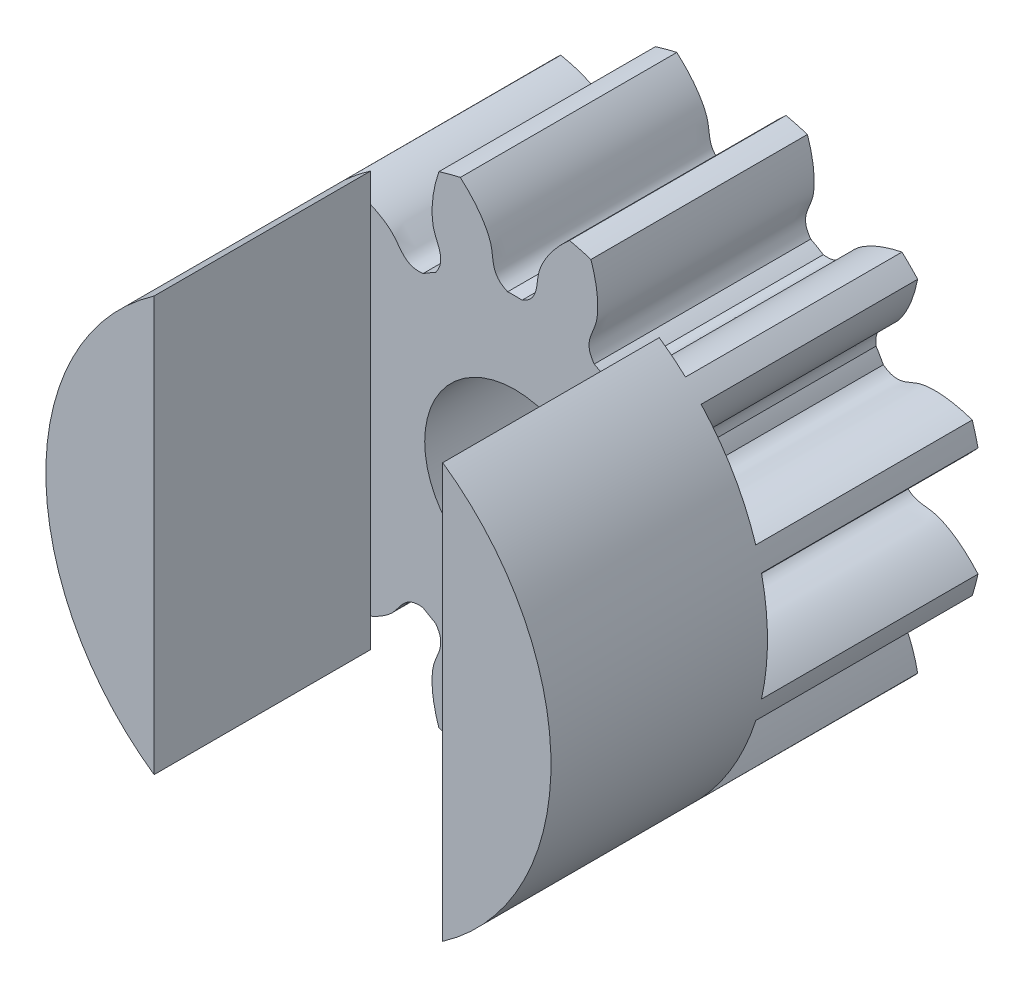
SolidWorks part; units mm, degrees
note: '?' marks a value the reader was unsure of.
ref_plane "前视基准面" through (0, 0, 0) normal (0, 0, 1) x (1, 0, 0)
ref_plane "上视基准面" through (0, 0, 0) normal (0, 1, 0) x (1, 0, 0)
ref_plane "右视基准面" through (0, 0, 0) normal (1, 0, 0) x (0, 0, -1)
sketch "草图1" plane through (0, 0, 0) normal (0, 0, 1) x (1, 0, 0)
  circle A0 centre (0, 0) radius 35
extrude "凸台-拉伸1" add sketch "草图1" along normal blind 30
ref_axis "基准轴1" through (0, 0, -1.5) along (0, 0, 1)?
sketch "草图2" plane through (0, 0, 0) normal (0, 0, 1) x (1, 0, 0)
  line L0 (0, 0) -> (0, 35) construction
  circle A0 centre (0, 0) radius 35 construction
  arc A1 (1.0042, 23.7288) -> (-1.0042, 23.7288) centre (0, 0) ccw
  arc A2 (17.488, 39.4749) -> (-17.488, 39.4749) centre (0, 0) ccw
  spline S0 degree 3 poles (1.0042, 23.7288) (3.4039, 24.7465) (2.8719, 26.7241) (3.3808, 28.4474) (3.4131, 28.5495) (3.4511, 28.6617) (3.4952, 28.7836) (3.5458, 28.9152) (3.6032, 29.0562) (3.6679, 29.2064) (3.7402, 29.3655) (3.8206, 29.5333) (3.9094, 29.7096) (4.0069, 29.894) (4.1136, 30.0862) (4.2298, 30.2861) (4.3558, 30.4932) (4.492, 30.7073) (4.6387, 30.928) (4.7962, 31.155) (4.9648, 31.3879) (5.1449, 31.6265) (5.3366, 31.8702) (5.5403, 32.1188) (5.7563, 32.3718) (5.9848, 32.6289) (6.226, 32.8897) (6.4802, 33.1537) (6.7476, 33.4205) (7.0285, 33.6897) (7.323, 33.9609) (7.6312, 34.2336) (7.9535, 34.5075) (8.2899, 34.7819) (8.6406, 35.0565) (9.0058, 35.3308) (9.3855, 35.6044) (9.7799, 35.8767) (10.189, 36.1473) (10.6131, 36.4157) (11.052, 36.6814) (11.5059, 36.9439) (11.9749, 37.2028) (12.4589, 37.4574) (12.958, 37.7074) (13.4722, 37.9522) (14.0015, 38.1913) (14.5458, 38.4242) (15.1051, 38.6504) (15.6793, 38.8694) (16.4719, 39.1536) (17.078, 39.3505) (17.488, 39.4749) knots 0 0 0 0 0.218015 0.222044 0.226546 0.231522 0.236972 0.242897 0.249295 0.256167 0.263513 0.271332 0.279626 0.288394 0.297636 0.307351 0.317541 0.328204 0.339341 0.350953 0.363038 0.375597 0.38863 0.402137 0.416118 0.430573 0.445502 0.460904 0.476781 0.493132 0.509956 0.527255 0.545027 0.563273 0.581994 0.601188 0.620856 0.640998 0.661614 0.682704 0.704268 0.726305 0.748817 0.771803 0.795262 0.819196 0.843603 0.868484 0.89384 0.919669 0.945972 1 1 1 1
  spline S1 degree 3 poles (-1.0042, 23.7288) (-3.4039, 24.7465) (-2.8719, 26.7241) (-3.3808, 28.4474) (-3.4131, 28.5495) (-3.4511, 28.6617) (-3.4952, 28.7836) (-3.5458, 28.9152) (-3.6032, 29.0562) (-3.6679, 29.2064) (-3.7402, 29.3655) (-3.8206, 29.5333) (-3.9094, 29.7096) (-4.0069, 29.894) (-4.1136, 30.0862) (-4.2298, 30.2861) (-4.3558, 30.4932) (-4.492, 30.7073) (-4.6387, 30.928) (-4.7962, 31.155) (-4.9648, 31.3879) (-5.1449, 31.6265) (-5.3366, 31.8702) (-5.5403, 32.1188) (-5.7563, 32.3718) (-5.9848, 32.6289) (-6.226, 32.8897) (-6.4802, 33.1537) (-6.7476, 33.4205) (-7.0285, 33.6897) (-7.323, 33.9609) (-7.6312, 34.2336) (-7.9535, 34.5075) (-8.2899, 34.7819) (-8.6406, 35.0565) (-9.0058, 35.3308) (-9.3855, 35.6044) (-9.7799, 35.8767) (-10.189, 36.1473) (-10.6131, 36.4157) (-11.052, 36.6814) (-11.5059, 36.9439) (-11.9749, 37.2028) (-12.4589, 37.4574) (-12.958, 37.7074) (-13.4722, 37.9522) (-14.0015, 38.1913) (-14.5458, 38.4242) (-15.1051, 38.6504) (-15.6793, 38.8694) (-16.4719, 39.1536) (-17.078, 39.3505) (-17.488, 39.4749) knots 0 0 0 0 0.218015 0.222044 0.226546 0.231522 0.236972 0.242897 0.249295 0.256167 0.263513 0.271332 0.279626 0.288394 0.297636 0.307351 0.317541 0.328204 0.339341 0.350953 0.363038 0.375597 0.38863 0.402137 0.416118 0.430573 0.445502 0.460904 0.476781 0.493132 0.509956 0.527255 0.545027 0.563273 0.581994 0.601188 0.620856 0.640998 0.661614 0.682704 0.704268 0.726305 0.748817 0.771803 0.795262 0.819196 0.843603 0.868484 0.89384 0.919669 0.945972 1 1 1 1
extrude "切除-拉伸1" cut sketch "草图2" along normal through all
pattern_circular "阵列(圆周)1" count 12 every 30 about axis through (0, 0, -1.5) along (0, 0, 1) of "切除-拉伸1"
sketch "草图3" plane through (0, 0, 0) normal (0, 0, 1) x (1, 0, 0)
  circle A0 centre (0, 0) radius 30 construction
  dimension "Dn" = 60
sketch "草图4" plane through (0, 0, 30) normal (0, 0, 1) x (1, 0, 0)
  circle A0 centre (0, 0) radius 1.3486
  arc M1 (-10.9947, 21.0518) -> (-12.734, 20.0476) centre (0, 0) ccw
  spline M2 degree 3 poles (-12.734, 20.0476) (-15.3212, 19.7292) (-15.8492, 21.7078) (-17.1515, 22.9458) (-17.2306, 23.0181) (-17.3196, 23.0962) (-17.4188, 23.1797) (-17.5283, 23.2684) (-17.6486, 23.3618) (-17.7797, 23.4595) (-17.9219, 23.5612) (-18.0754, 23.6663) (-18.2404, 23.7746) (-18.4171, 23.8855) (-18.6056, 23.9986) (-18.8062, 24.1136) (-19.0189, 24.23) (-19.2439, 24.3473) (-19.4813, 24.4651) (-19.7312, 24.5829) (-19.9936, 24.7003) (-20.2688, 24.8169) (-20.5567, 24.9321) (-20.8575, 25.0455) (-21.171, 25.1567) (-21.4974, 25.2651) (-21.8367, 25.3703) (-22.1889, 25.4718) (-22.5539, 25.5692) (-22.9317, 25.6619) (-23.3223, 25.7495) (-23.7257, 25.8316) (-24.1417, 25.9076) (-24.5702, 25.9771) (-25.0113, 26.0395) (-25.4647, 26.0945) (-25.9303, 26.1416) (-26.408, 26.1802) (-26.8976, 26.21) (-27.399, 26.2304) (-27.912, 26.241) (-28.4364, 26.2414) (-28.9719, 26.2311) (-29.5185, 26.2096) (-30.0757, 26.1765) (-30.6434, 26.1314) (-31.2213, 26.0739) (-31.8091, 26.0034) (-32.4066, 25.9197) (-33.0134, 25.8222) (-33.8419, 25.6721) (-34.4652, 25.5396) (-34.8825, 25.4422) knots 0 0 0 0 0.218015 0.222044 0.226546 0.231522 0.236972 0.242897 0.249295 0.256167 0.263513 0.271332 0.279626 0.288394 0.297636 0.307351 0.317541 0.328204 0.339341 0.350953 0.363038 0.375597 0.38863 0.402137 0.416118 0.430573 0.445502 0.460904 0.476781 0.493132 0.509956 0.527255 0.545027 0.563273 0.581994 0.601188 0.620856 0.640998 0.661614 0.682704 0.704268 0.726305 0.748817 0.771803 0.795262 0.819196 0.843603 0.868484 0.89384 0.919669 0.945972 1 1 1 1 only from (-12.734, 20.0476) to (-23.6368, 25.8128)
  arc M3 (-23.6368, 25.8128) -> (-25.8128, 23.6368) centre (0, 0) ccw
  spline M4 degree 3 poles (-25.4422, 34.8825) (-25.5396, 34.4652) (-25.6721, 33.8419) (-25.8222, 33.0134) (-25.9197, 32.4066) (-26.0034, 31.8091) (-26.0739, 31.2213) (-26.1314, 30.6434) (-26.1765, 30.0757) (-26.2096, 29.5185) (-26.2311, 28.9719) (-26.2414, 28.4364) (-26.241, 27.912) (-26.2304, 27.399) (-26.21, 26.8976) (-26.1802, 26.408) (-26.1416, 25.9303) (-26.0945, 25.4647) (-26.0395, 25.0113) (-25.9771, 24.5702) (-25.9076, 24.1417) (-25.8316, 23.7257) (-25.7495, 23.3223) (-25.6619, 22.9317) (-25.5692, 22.5539) (-25.4718, 22.1889) (-25.3703, 21.8367) (-25.2651, 21.4974) (-25.1567, 21.171) (-25.0455, 20.8575) (-24.9321, 20.5567) (-24.8169, 20.2688) (-24.7003, 19.9936) (-24.5829, 19.7312) (-24.4651, 19.4813) (-24.3473, 19.2439) (-24.23, 19.0189) (-24.1136, 18.8062) (-23.9986, 18.6056) (-23.8855, 18.4171) (-23.7746, 18.2404) (-23.6663, 18.0754) (-23.5612, 17.9219) (-23.4595, 17.7797) (-23.3618, 17.6486) (-23.2684, 17.5283) (-23.1797, 17.4188) (-23.0962, 17.3196) (-23.0181, 17.2306) (-22.9458, 17.1515) (-21.7078, 15.8492) (-19.7292, 15.3212) (-20.0476, 12.734) knots 0 0 0 0 0.054028 0.080331 0.10616 0.131516 0.156397 0.180804 0.204738 0.228197 0.251183 0.273695 0.295732 0.317296 0.338386 0.359002 0.379144 0.398812 0.418006 0.436727 0.454973 0.472745 0.490044 0.506868 0.523219 0.539096 0.554498 0.569427 0.583882 0.597863 0.61137 0.624403 0.636962 0.649047 0.660659 0.671796 0.682459 0.692649 0.702364 0.711606 0.720374 0.728668 0.736487 0.743833 0.750705 0.757103 0.763028 0.768478 0.773454 0.777956 0.781985 1 1 1 1 only from (-25.8128, 23.6368) to (-20.0476, 12.734)
  arc M5 (-20.0476, 12.734) -> (-21.0518, 10.9947) centre (0, 0) ccw
  spline M6 degree 3 poles (-21.0518, 10.9947) (-23.1331, 9.4254) (-24.5797, 10.8749) (-26.3266, 11.2959) (-26.4312, 11.3189) (-26.5473, 11.3421) (-26.675, 11.3649) (-26.8142, 11.3869) (-26.965, 11.4077) (-27.1274, 11.4267) (-27.3014, 11.4436) (-27.4869, 11.4579) (-27.6839, 11.4692) (-27.8924, 11.4769) (-28.1123, 11.4806) (-28.3434, 11.4799) (-28.5858, 11.4743) (-28.8393, 11.4634) (-29.1038, 11.4468) (-29.3791, 11.4239) (-29.6652, 11.3943) (-29.9618, 11.3576) (-30.2687, 11.3135) (-30.5858, 11.2613) (-30.913, 11.2008) (-31.2498, 11.1315) (-31.5963, 11.053) (-31.952, 10.9648) (-32.3168, 10.8666) (-32.6904, 10.758) (-33.0725, 10.6386) (-33.4628, 10.508) (-33.8611, 10.3658) (-34.267, 10.2117) (-34.6802, 10.0453) (-35.1003, 9.8662) (-35.5271, 9.6741) (-35.9601, 9.4687) (-36.399, 9.2497) (-36.8435, 9.0167) (-37.293, 8.7694) (-37.7473, 8.5075) (-38.206, 8.2308) (-38.6685, 7.939) (-39.1346, 7.6317) (-39.6037, 7.3088) (-40.0754, 6.97) (-40.5492, 6.6151) (-41.0248, 6.2438) (-41.5015, 5.856) (-42.144, 5.3117) (-42.6175, 4.8853) (-42.9302, 4.5924) knots 0 0 0 0 0.218015 0.222044 0.226546 0.231522 0.236972 0.242897 0.249295 0.256167 0.263513 0.271332 0.279626 0.288394 0.297636 0.307351 0.317541 0.328204 0.339341 0.350953 0.363038 0.375597 0.38863 0.402137 0.416118 0.430573 0.445502 0.460904 0.476781 0.493132 0.509956 0.527255 0.545027 0.563273 0.581994 0.601188 0.620856 0.640998 0.661614 0.682704 0.704268 0.726305 0.748817 0.771803 0.795262 0.819196 0.843603 0.868484 0.89384 0.919669 0.945972 1 1 1 1 only from (-21.0518, 10.9947) to (-33.3765, 10.5362)
  arc M7 (-33.3765, 10.5362) -> (-34.173, 7.5637) centre (0, 0) ccw
  spline M8 degree 3 poles (-39.4749, 17.488) (-39.3505, 17.078) (-39.1536, 16.4719) (-38.8694, 15.6793) (-38.6504, 15.1051) (-38.4242, 14.5458) (-38.1913, 14.0015) (-37.9522, 13.4722) (-37.7074, 12.958) (-37.4574, 12.4589) (-37.2028, 11.9749) (-36.9439, 11.5059) (-36.6814, 11.052) (-36.4157, 10.6131) (-36.1473, 10.189) (-35.8767, 9.7799) (-35.6044, 9.3855) (-35.3308, 9.0058) (-35.0565, 8.6406) (-34.7819, 8.2899) (-34.5075, 7.9535) (-34.2336, 7.6312) (-33.9609, 7.323) (-33.6897, 7.0285) (-33.4205, 6.7476) (-33.1537, 6.4802) (-32.8897, 6.226) (-32.6289, 5.9848) (-32.3718, 5.7563) (-32.1188, 5.5403) (-31.8702, 5.3366) (-31.6265, 5.1449) (-31.3879, 4.9648) (-31.155, 4.7962) (-30.928, 4.6387) (-30.7073, 4.492) (-30.4932, 4.3558) (-30.2861, 4.2298) (-30.0862, 4.1136) (-29.894, 4.0069) (-29.7096, 3.9094) (-29.5333, 3.8206) (-29.3655, 3.7402) (-29.2064, 3.6679) (-29.0562, 3.6032) (-28.9152, 3.5458) (-28.7836, 3.4952) (-28.6617, 3.4511) (-28.5495, 3.4131) (-28.4474, 3.3808) (-26.7241, 2.8719) (-24.7465, 3.4039) (-23.7288, 1.0042) knots 0 0 0 0 0.054028 0.080331 0.10616 0.131516 0.156397 0.180804 0.204738 0.228197 0.251183 0.273695 0.295732 0.317296 0.338386 0.359002 0.379144 0.398812 0.418006 0.436727 0.454973 0.472745 0.490044 0.506868 0.523219 0.539096 0.554498 0.569427 0.583882 0.597863 0.61137 0.624403 0.636962 0.649047 0.660659 0.671796 0.682459 0.692649 0.702364 0.711606 0.720374 0.728668 0.736487 0.743833 0.750705 0.757103 0.763028 0.768478 0.773454 0.777956 0.781985 1 1 1 1 only from (-34.173, 7.5637) to (-23.7288, 1.0042)
  arc M9 (-23.7288, 1.0042) -> (-23.7288, -1.0042) centre (0, 0) ccw
  spline M10 degree 3 poles (-23.7288, -1.0042) (-24.7465, -3.4039) (-26.7241, -2.8719) (-28.4474, -3.3808) (-28.5495, -3.4131) (-28.6617, -3.4511) (-28.7836, -3.4952) (-28.9152, -3.5458) (-29.0562, -3.6032) (-29.2064, -3.6679) (-29.3655, -3.7402) (-29.5333, -3.8206) (-29.7096, -3.9094) (-29.894, -4.0069) (-30.0862, -4.1136) (-30.2861, -4.2298) (-30.4932, -4.3558) (-30.7073, -4.492) (-30.928, -4.6387) (-31.155, -4.7962) (-31.3879, -4.9648) (-31.6265, -5.1449) (-31.8702, -5.3366) (-32.1188, -5.5403) (-32.3718, -5.7563) (-32.6289, -5.9848) (-32.8897, -6.226) (-33.1537, -6.4802) (-33.4205, -6.7476) (-33.6897, -7.0285) (-33.9609, -7.323) (-34.2336, -7.6312) (-34.5075, -7.9535) (-34.7819, -8.2899) (-35.0565, -8.6406) (-35.3308, -9.0058) (-35.6044, -9.3855) (-35.8767, -9.7799) (-36.1473, -10.189) (-36.4157, -10.6131) (-36.6814, -11.052) (-36.9439, -11.5059) (-37.2028, -11.9749) (-37.4574, -12.4589) (-37.7074, -12.958) (-37.9522, -13.4722) (-38.1913, -14.0015) (-38.4242, -14.5458) (-38.6504, -15.1051) (-38.8694, -15.6793) (-39.1536, -16.4719) (-39.3505, -17.078) (-39.4749, -17.488) knots 0 0 0 0 0.218015 0.222044 0.226546 0.231522 0.236972 0.242897 0.249295 0.256167 0.263513 0.271332 0.279626 0.288394 0.297636 0.307351 0.317541 0.328204 0.339341 0.350953 0.363038 0.375597 0.38863 0.402137 0.416118 0.430573 0.445502 0.460904 0.476781 0.493132 0.509956 0.527255 0.545027 0.563273 0.581994 0.601188 0.620856 0.640998 0.661614 0.682704 0.704268 0.726305 0.748817 0.771803 0.795262 0.819196 0.843603 0.868484 0.89384 0.919669 0.945972 1 1 1 1 only from (-23.7288, -1.0042) to (-34.173, -7.5637)
  arc M11 (-34.173, -7.5637) -> (-33.3765, -10.5362) centre (0, 0) ccw
  spline M12 degree 3 poles (-42.9302, -4.5924) (-42.6175, -4.8853) (-42.144, -5.3117) (-41.5015, -5.856) (-41.0248, -6.2438) (-40.5492, -6.6151) (-40.0754, -6.97) (-39.6037, -7.3088) (-39.1346, -7.6317) (-38.6685, -7.939) (-38.206, -8.2308) (-37.7473, -8.5075) (-37.293, -8.7694) (-36.8435, -9.0167) (-36.399, -9.2497) (-35.9601, -9.4687) (-35.5271, -9.6741) (-35.1003, -9.8662) (-34.6802, -10.0453) (-34.267, -10.2117) (-33.8611, -10.3658) (-33.4628, -10.508) (-33.0725, -10.6386) (-32.6904, -10.758) (-32.3168, -10.8666) (-31.952, -10.9648) (-31.5963, -11.053) (-31.2498, -11.1315) (-30.913, -11.2008) (-30.5858, -11.2613) (-30.2687, -11.3135) (-29.9618, -11.3576) (-29.6652, -11.3943) (-29.3791, -11.4239) (-29.1038, -11.4468) (-28.8393, -11.4634) (-28.5858, -11.4743) (-28.3434, -11.4799) (-28.1123, -11.4806) (-27.8924, -11.4769) (-27.6839, -11.4692) (-27.4869, -11.4579) (-27.3014, -11.4436) (-27.1274, -11.4267) (-26.965, -11.4077) (-26.8142, -11.3869) (-26.675, -11.3649) (-26.5473, -11.3421) (-26.4312, -11.3189) (-26.3266, -11.2959) (-24.5797, -10.8749) (-23.1331, -9.4254) (-21.0518, -10.9947) knots 0 0 0 0 0.054028 0.080331 0.10616 0.131516 0.156397 0.180804 0.204738 0.228197 0.251183 0.273695 0.295732 0.317296 0.338386 0.359002 0.379144 0.398812 0.418006 0.436727 0.454973 0.472745 0.490044 0.506868 0.523219 0.539096 0.554498 0.569427 0.583882 0.597863 0.61137 0.624403 0.636962 0.649047 0.660659 0.671796 0.682459 0.692649 0.702364 0.711606 0.720374 0.728668 0.736487 0.743833 0.750705 0.757103 0.763028 0.768478 0.773454 0.777956 0.781985 1 1 1 1 only from (-33.3765, -10.5362) to (-21.0518, -10.9947)
  arc M13 (-21.0518, -10.9947) -> (-20.0476, -12.734) centre (0, 0) ccw
  spline M14 degree 3 poles (-20.0476, -12.734) (-19.7292, -15.3212) (-21.7078, -15.8492) (-22.9458, -17.1515) (-23.0181, -17.2306) (-23.0962, -17.3196) (-23.1797, -17.4188) (-23.2684, -17.5283) (-23.3618, -17.6486) (-23.4595, -17.7797) (-23.5612, -17.9219) (-23.6663, -18.0754) (-23.7746, -18.2404) (-23.8855, -18.4171) (-23.9986, -18.6056) (-24.1136, -18.8062) (-24.23, -19.0189) (-24.3473, -19.2439) (-24.4651, -19.4813) (-24.5829, -19.7312) (-24.7003, -19.9936) (-24.8169, -20.2688) (-24.9321, -20.5567) (-25.0455, -20.8575) (-25.1567, -21.171) (-25.2651, -21.4974) (-25.3703, -21.8367) (-25.4718, -22.1889) (-25.5692, -22.5539) (-25.6619, -22.9317) (-25.7495, -23.3223) (-25.8316, -23.7257) (-25.9076, -24.1417) (-25.9771, -24.5702) (-26.0395, -25.0113) (-26.0945, -25.4647) (-26.1416, -25.9303) (-26.1802, -26.408) (-26.21, -26.8976) (-26.2304, -27.399) (-26.241, -27.912) (-26.2414, -28.4364) (-26.2311, -28.9719) (-26.2096, -29.5185) (-26.1765, -30.0757) (-26.1314, -30.6434) (-26.0739, -31.2213) (-26.0034, -31.8091) (-25.9197, -32.4066) (-25.8222, -33.0134) (-25.6721, -33.8419) (-25.5396, -34.4652) (-25.4422, -34.8825) knots 0 0 0 0 0.218015 0.222044 0.226546 0.231522 0.236972 0.242897 0.249295 0.256167 0.263513 0.271332 0.279626 0.288394 0.297636 0.307351 0.317541 0.328204 0.339341 0.350953 0.363038 0.375597 0.38863 0.402137 0.416118 0.430573 0.445502 0.460904 0.476781 0.493132 0.509956 0.527255 0.545027 0.563273 0.581994 0.601188 0.620856 0.640998 0.661614 0.682704 0.704268 0.726305 0.748817 0.771803 0.795262 0.819196 0.843603 0.868484 0.89384 0.919669 0.945972 1 1 1 1 only from (-20.0476, -12.734) to (-25.8128, -23.6368)
  arc M15 (-25.8128, -23.6368) -> (-23.6368, -25.8128) centre (0, 0) ccw
  spline M16 degree 3 poles (-34.8825, -25.4422) (-34.4652, -25.5396) (-33.8419, -25.6721) (-33.0134, -25.8222) (-32.4066, -25.9197) (-31.8091, -26.0034) (-31.2213, -26.0739) (-30.6434, -26.1314) (-30.0757, -26.1765) (-29.5185, -26.2096) (-28.9719, -26.2311) (-28.4364, -26.2414) (-27.912, -26.241) (-27.399, -26.2304) (-26.8976, -26.21) (-26.408, -26.1802) (-25.9303, -26.1416) (-25.4647, -26.0945) (-25.0113, -26.0395) (-24.5702, -25.9771) (-24.1417, -25.9076) (-23.7257, -25.8316) (-23.3223, -25.7495) (-22.9317, -25.6619) (-22.5539, -25.5692) (-22.1889, -25.4718) (-21.8367, -25.3703) (-21.4974, -25.2651) (-21.171, -25.1567) (-20.8575, -25.0455) (-20.5567, -24.9321) (-20.2688, -24.8169) (-19.9936, -24.7003) (-19.7312, -24.5829) (-19.4813, -24.4651) (-19.2439, -24.3473) (-19.0189, -24.23) (-18.8062, -24.1136) (-18.6056, -23.9986) (-18.4171, -23.8855) (-18.2404, -23.7746) (-18.0754, -23.6663) (-17.9219, -23.5612) (-17.7797, -23.4595) (-17.6486, -23.3618) (-17.5283, -23.2684) (-17.4188, -23.1797) (-17.3196, -23.0962) (-17.2306, -23.0181) (-17.1515, -22.9458) (-15.8492, -21.7078) (-15.3212, -19.7292) (-12.734, -20.0476) knots 0 0 0 0 0.054028 0.080331 0.10616 0.131516 0.156397 0.180804 0.204738 0.228197 0.251183 0.273695 0.295732 0.317296 0.338386 0.359002 0.379144 0.398812 0.418006 0.436727 0.454973 0.472745 0.490044 0.506868 0.523219 0.539096 0.554498 0.569427 0.583882 0.597863 0.61137 0.624403 0.636962 0.649047 0.660659 0.671796 0.682459 0.692649 0.702364 0.711606 0.720374 0.728668 0.736487 0.743833 0.750705 0.757103 0.763028 0.768478 0.773454 0.777956 0.781985 1 1 1 1 only from (-23.6368, -25.8128) to (-12.734, -20.0476)
  arc M17 (-12.734, -20.0476) -> (-10.9947, -21.0518) centre (0, 0) ccw
  spline M18 degree 3 poles (-10.9947, -21.0518) (-9.4254, -23.1331) (-10.8749, -24.5797) (-11.2959, -26.3266) (-11.3189, -26.4312) (-11.3421, -26.5473) (-11.3649, -26.675) (-11.3869, -26.8142) (-11.4077, -26.965) (-11.4267, -27.1274) (-11.4436, -27.3014) (-11.4579, -27.4869) (-11.4692, -27.6839) (-11.4769, -27.8924) (-11.4806, -28.1123) (-11.4799, -28.3434) (-11.4743, -28.5858) (-11.4634, -28.8393) (-11.4468, -29.1038) (-11.4239, -29.3791) (-11.3943, -29.6652) (-11.3576, -29.9618) (-11.3135, -30.2687) (-11.2613, -30.5858) (-11.2008, -30.913) (-11.1315, -31.2498) (-11.053, -31.5963) (-10.9648, -31.952) (-10.8666, -32.3168) (-10.758, -32.6904) (-10.6386, -33.0725) (-10.508, -33.4628) (-10.3658, -33.8611) (-10.2117, -34.267) (-10.0453, -34.6802) (-9.8662, -35.1003) (-9.6741, -35.5271) (-9.4687, -35.9601) (-9.2497, -36.399) (-9.0167, -36.8435) (-8.7694, -37.293) (-8.5075, -37.7473) (-8.2308, -38.206) (-7.939, -38.6685) (-7.6317, -39.1346) (-7.3088, -39.6037) (-6.97, -40.0754) (-6.6151, -40.5492) (-6.2438, -41.0248) (-5.856, -41.5015) (-5.3117, -42.144) (-4.8853, -42.6175) (-4.5924, -42.9302) knots 0 0 0 0 0.218015 0.222044 0.226546 0.231522 0.236972 0.242897 0.249295 0.256167 0.263513 0.271332 0.279626 0.288394 0.297636 0.307351 0.317541 0.328204 0.339341 0.350953 0.363038 0.375597 0.38863 0.402137 0.416118 0.430573 0.445502 0.460904 0.476781 0.493132 0.509956 0.527255 0.545027 0.563273 0.581994 0.601188 0.620856 0.640998 0.661614 0.682704 0.704268 0.726305 0.748817 0.771803 0.795262 0.819196 0.843603 0.868484 0.89384 0.919669 0.945972 1 1 1 1 only from (-10.9947, -21.0518) to (-10.5362, -33.3765)
  arc M19 (-10.5362, -33.3765) -> (-7.5637, -34.173) centre (0, 0) ccw
  spline M20 degree 3 poles (-17.488, -39.4749) (-17.078, -39.3505) (-16.4719, -39.1536) (-15.6793, -38.8694) (-15.1051, -38.6504) (-14.5458, -38.4242) (-14.0015, -38.1913) (-13.4722, -37.9522) (-12.958, -37.7074) (-12.4589, -37.4574) (-11.9749, -37.2028) (-11.5059, -36.9439) (-11.052, -36.6814) (-10.6131, -36.4157) (-10.189, -36.1473) (-9.7799, -35.8767) (-9.3855, -35.6044) (-9.0058, -35.3308) (-8.6406, -35.0565) (-8.2899, -34.7819) (-7.9535, -34.5075) (-7.6312, -34.2336) (-7.323, -33.9609) (-7.0285, -33.6897) (-6.7476, -33.4205) (-6.4802, -33.1537) (-6.226, -32.8897) (-5.9848, -32.6289) (-5.7563, -32.3718) (-5.5403, -32.1188) (-5.3366, -31.8702) (-5.1449, -31.6265) (-4.9648, -31.3879) (-4.7962, -31.155) (-4.6387, -30.928) (-4.492, -30.7073) (-4.3558, -30.4932) (-4.2298, -30.2861) (-4.1136, -30.0862) (-4.0069, -29.894) (-3.9094, -29.7096) (-3.8206, -29.5333) (-3.7402, -29.3655) (-3.6679, -29.2064) (-3.6032, -29.0562) (-3.5458, -28.9152) (-3.4952, -28.7836) (-3.4511, -28.6617) (-3.4131, -28.5495) (-3.3808, -28.4474) (-2.8719, -26.7241) (-3.4039, -24.7465) (-1.0042, -23.7288) knots 0 0 0 0 0.054028 0.080331 0.10616 0.131516 0.156397 0.180804 0.204738 0.228197 0.251183 0.273695 0.295732 0.317296 0.338386 0.359002 0.379144 0.398812 0.418006 0.436727 0.454973 0.472745 0.490044 0.506868 0.523219 0.539096 0.554498 0.569427 0.583882 0.597863 0.61137 0.624403 0.636962 0.649047 0.660659 0.671796 0.682459 0.692649 0.702364 0.711606 0.720374 0.728668 0.736487 0.743833 0.750705 0.757103 0.763028 0.768478 0.773454 0.777956 0.781985 1 1 1 1 only from (-7.5637, -34.173) to (-1.0042, -23.7288)
  arc M21 (-1.0042, -23.7288) -> (1.0042, -23.7288) centre (0, 0) ccw
  spline M22 degree 3 poles (1.0042, -23.7288) (3.4039, -24.7465) (2.8719, -26.7241) (3.3808, -28.4474) (3.4131, -28.5495) (3.4511, -28.6617) (3.4952, -28.7836) (3.5458, -28.9152) (3.6032, -29.0562) (3.6679, -29.2064) (3.7402, -29.3655) (3.8206, -29.5333) (3.9094, -29.7096) (4.0069, -29.894) (4.1136, -30.0862) (4.2298, -30.2861) (4.3558, -30.4932) (4.492, -30.7073) (4.6387, -30.928) (4.7962, -31.155) (4.9648, -31.3879) (5.1449, -31.6265) (5.3366, -31.8702) (5.5403, -32.1188) (5.7563, -32.3718) (5.9848, -32.6289) (6.226, -32.8897) (6.4802, -33.1537) (6.7476, -33.4205) (7.0285, -33.6897) (7.323, -33.9609) (7.6312, -34.2336) (7.9535, -34.5075) (8.2899, -34.7819) (8.6406, -35.0565) (9.0058, -35.3308) (9.3855, -35.6044) (9.7799, -35.8767) (10.189, -36.1473) (10.6131, -36.4157) (11.052, -36.6814) (11.5059, -36.9439) (11.9749, -37.2028) (12.4589, -37.4574) (12.958, -37.7074) (13.4722, -37.9522) (14.0015, -38.1913) (14.5458, -38.4242) (15.1051, -38.6504) (15.6793, -38.8694) (16.4719, -39.1536) (17.078, -39.3505) (17.488, -39.4749) knots 0 0 0 0 0.218015 0.222044 0.226546 0.231522 0.236972 0.242897 0.249295 0.256167 0.263513 0.271332 0.279626 0.288394 0.297636 0.307351 0.317541 0.328204 0.339341 0.350953 0.363038 0.375597 0.38863 0.402137 0.416118 0.430573 0.445502 0.460904 0.476781 0.493132 0.509956 0.527255 0.545027 0.563273 0.581994 0.601188 0.620856 0.640998 0.661614 0.682704 0.704268 0.726305 0.748817 0.771803 0.795262 0.819196 0.843603 0.868484 0.89384 0.919669 0.945972 1 1 1 1 only from (1.0042, -23.7288) to (7.5637, -34.173)
  arc M23 (7.5637, -34.173) -> (10.5362, -33.3765) centre (0, 0) ccw
  spline M24 degree 3 poles (4.5924, -42.9302) (4.8853, -42.6175) (5.3117, -42.144) (5.856, -41.5015) (6.2438, -41.0248) (6.6151, -40.5492) (6.97, -40.0754) (7.3088, -39.6037) (7.6317, -39.1346) (7.939, -38.6685) (8.2308, -38.206) (8.5075, -37.7473) (8.7694, -37.293) (9.0167, -36.8435) (9.2497, -36.399) (9.4687, -35.9601) (9.6741, -35.5271) (9.8662, -35.1003) (10.0453, -34.6802) (10.2117, -34.267) (10.3658, -33.8611) (10.508, -33.4628) (10.6386, -33.0725) (10.758, -32.6904) (10.8666, -32.3168) (10.9648, -31.952) (11.053, -31.5963) (11.1315, -31.2498) (11.2008, -30.913) (11.2613, -30.5858) (11.3135, -30.2687) (11.3576, -29.9618) (11.3943, -29.6652) (11.4239, -29.3791) (11.4468, -29.1038) (11.4634, -28.8393) (11.4743, -28.5858) (11.4799, -28.3434) (11.4806, -28.1123) (11.4769, -27.8924) (11.4692, -27.6839) (11.4579, -27.4869) (11.4436, -27.3014) (11.4267, -27.1274) (11.4077, -26.965) (11.3869, -26.8142) (11.3649, -26.675) (11.3421, -26.5473) (11.3189, -26.4312) (11.2959, -26.3266) (10.8749, -24.5797) (9.4254, -23.1331) (10.9947, -21.0518) knots 0 0 0 0 0.054028 0.080331 0.10616 0.131516 0.156397 0.180804 0.204738 0.228197 0.251183 0.273695 0.295732 0.317296 0.338386 0.359002 0.379144 0.398812 0.418006 0.436727 0.454973 0.472745 0.490044 0.506868 0.523219 0.539096 0.554498 0.569427 0.583882 0.597863 0.61137 0.624403 0.636962 0.649047 0.660659 0.671796 0.682459 0.692649 0.702364 0.711606 0.720374 0.728668 0.736487 0.743833 0.750705 0.757103 0.763028 0.768478 0.773454 0.777956 0.781985 1 1 1 1 only from (10.5362, -33.3765) to (10.9947, -21.0518)
  arc M25 (10.9947, -21.0518) -> (12.734, -20.0476) centre (0, 0) ccw
  spline M26 degree 3 poles (12.734, -20.0476) (15.3212, -19.7292) (15.8492, -21.7078) (17.1515, -22.9458) (17.2306, -23.0181) (17.3196, -23.0962) (17.4188, -23.1797) (17.5283, -23.2684) (17.6486, -23.3618) (17.7797, -23.4595) (17.9219, -23.5612) (18.0754, -23.6663) (18.2404, -23.7746) (18.4171, -23.8855) (18.6056, -23.9986) (18.8062, -24.1136) (19.0189, -24.23) (19.2439, -24.3473) (19.4813, -24.4651) (19.7312, -24.5829) (19.9936, -24.7003) (20.2688, -24.8169) (20.5567, -24.9321) (20.8575, -25.0455) (21.171, -25.1567) (21.4974, -25.2651) (21.8367, -25.3703) (22.1889, -25.4718) (22.5539, -25.5692) (22.9317, -25.6619) (23.3223, -25.7495) (23.7257, -25.8316) (24.1417, -25.9076) (24.5702, -25.9771) (25.0113, -26.0395) (25.4647, -26.0945) (25.9303, -26.1416) (26.408, -26.1802) (26.8976, -26.21) (27.399, -26.2304) (27.912, -26.241) (28.4364, -26.2414) (28.9719, -26.2311) (29.5185, -26.2096) (30.0757, -26.1765) (30.6434, -26.1314) (31.2213, -26.0739) (31.8091, -26.0034) (32.4066, -25.9197) (33.0134, -25.8222) (33.8419, -25.6721) (34.4652, -25.5396) (34.8825, -25.4422) knots 0 0 0 0 0.218015 0.222044 0.226546 0.231522 0.236972 0.242897 0.249295 0.256167 0.263513 0.271332 0.279626 0.288394 0.297636 0.307351 0.317541 0.328204 0.339341 0.350953 0.363038 0.375597 0.38863 0.402137 0.416118 0.430573 0.445502 0.460904 0.476781 0.493132 0.509956 0.527255 0.545027 0.563273 0.581994 0.601188 0.620856 0.640998 0.661614 0.682704 0.704268 0.726305 0.748817 0.771803 0.795262 0.819196 0.843603 0.868484 0.89384 0.919669 0.945972 1 1 1 1 only from (12.734, -20.0476) to (23.6368, -25.8128)
  arc M27 (23.6368, -25.8128) -> (25.8128, -23.6368) centre (0, 0) ccw
  spline M28 degree 3 poles (25.4422, -34.8825) (25.5396, -34.4652) (25.6721, -33.8419) (25.8222, -33.0134) (25.9197, -32.4066) (26.0034, -31.8091) (26.0739, -31.2213) (26.1314, -30.6434) (26.1765, -30.0757) (26.2096, -29.5185) (26.2311, -28.9719) (26.2414, -28.4364) (26.241, -27.912) (26.2304, -27.399) (26.21, -26.8976) (26.1802, -26.408) (26.1416, -25.9303) (26.0945, -25.4647) (26.0395, -25.0113) (25.9771, -24.5702) (25.9076, -24.1417) (25.8316, -23.7257) (25.7495, -23.3223) (25.6619, -22.9317) (25.5692, -22.5539) (25.4718, -22.1889) (25.3703, -21.8367) (25.2651, -21.4974) (25.1567, -21.171) (25.0455, -20.8575) (24.9321, -20.5567) (24.8169, -20.2688) (24.7003, -19.9936) (24.5829, -19.7312) (24.4651, -19.4813) (24.3473, -19.2439) (24.23, -19.0189) (24.1136, -18.8062) (23.9986, -18.6056) (23.8855, -18.4171) (23.7746, -18.2404) (23.6663, -18.0754) (23.5612, -17.9219) (23.4595, -17.7797) (23.3618, -17.6486) (23.2684, -17.5283) (23.1797, -17.4188) (23.0962, -17.3196) (23.0181, -17.2306) (22.9458, -17.1515) (21.7078, -15.8492) (19.7292, -15.3212) (20.0476, -12.734) knots 0 0 0 0 0.054028 0.080331 0.10616 0.131516 0.156397 0.180804 0.204738 0.228197 0.251183 0.273695 0.295732 0.317296 0.338386 0.359002 0.379144 0.398812 0.418006 0.436727 0.454973 0.472745 0.490044 0.506868 0.523219 0.539096 0.554498 0.569427 0.583882 0.597863 0.61137 0.624403 0.636962 0.649047 0.660659 0.671796 0.682459 0.692649 0.702364 0.711606 0.720374 0.728668 0.736487 0.743833 0.750705 0.757103 0.763028 0.768478 0.773454 0.777956 0.781985 1 1 1 1 only from (25.8128, -23.6368) to (20.0476, -12.734)
  arc M29 (20.0476, -12.734) -> (21.0518, -10.9947) centre (0, 0) ccw
  spline M30 degree 3 poles (21.0518, -10.9947) (23.1331, -9.4254) (24.5797, -10.8749) (26.3266, -11.2959) (26.4312, -11.3189) (26.5473, -11.3421) (26.675, -11.3649) (26.8142, -11.3869) (26.965, -11.4077) (27.1274, -11.4267) (27.3014, -11.4436) (27.4869, -11.4579) (27.6839, -11.4692) (27.8924, -11.4769) (28.1123, -11.4806) (28.3434, -11.4799) (28.5858, -11.4743) (28.8393, -11.4634) (29.1038, -11.4468) (29.3791, -11.4239) (29.6652, -11.3943) (29.9618, -11.3576) (30.2687, -11.3135) (30.5858, -11.2613) (30.913, -11.2008) (31.2498, -11.1315) (31.5963, -11.053) (31.952, -10.9648) (32.3168, -10.8666) (32.6904, -10.758) (33.0725, -10.6386) (33.4628, -10.508) (33.8611, -10.3658) (34.267, -10.2117) (34.6802, -10.0453) (35.1003, -9.8662) (35.5271, -9.6741) (35.9601, -9.4687) (36.399, -9.2497) (36.8435, -9.0167) (37.293, -8.7694) (37.7473, -8.5075) (38.206, -8.2308) (38.6685, -7.939) (39.1346, -7.6317) (39.6037, -7.3088) (40.0754, -6.97) (40.5492, -6.6151) (41.0248, -6.2438) (41.5015, -5.856) (42.144, -5.3117) (42.6175, -4.8853) (42.9302, -4.5924) knots 0 0 0 0 0.218015 0.222044 0.226546 0.231522 0.236972 0.242897 0.249295 0.256167 0.263513 0.271332 0.279626 0.288394 0.297636 0.307351 0.317541 0.328204 0.339341 0.350953 0.363038 0.375597 0.38863 0.402137 0.416118 0.430573 0.445502 0.460904 0.476781 0.493132 0.509956 0.527255 0.545027 0.563273 0.581994 0.601188 0.620856 0.640998 0.661614 0.682704 0.704268 0.726305 0.748817 0.771803 0.795262 0.819196 0.843603 0.868484 0.89384 0.919669 0.945972 1 1 1 1 only from (21.0518, -10.9947) to (33.3765, -10.5362)
  arc M31 (33.3765, -10.5362) -> (34.173, -7.5637) centre (0, 0) ccw
  spline M32 degree 3 poles (39.4749, -17.488) (39.3505, -17.078) (39.1536, -16.4719) (38.8694, -15.6793) (38.6504, -15.1051) (38.4242, -14.5458) (38.1913, -14.0015) (37.9522, -13.4722) (37.7074, -12.958) (37.4574, -12.4589) (37.2028, -11.9749) (36.9439, -11.5059) (36.6814, -11.052) (36.4157, -10.6131) (36.1473, -10.189) (35.8767, -9.7799) (35.6044, -9.3855) (35.3308, -9.0058) (35.0565, -8.6406) (34.7819, -8.2899) (34.5075, -7.9535) (34.2336, -7.6312) (33.9609, -7.323) (33.6897, -7.0285) (33.4205, -6.7476) (33.1537, -6.4802) (32.8897, -6.226) (32.6289, -5.9848) (32.3718, -5.7563) (32.1188, -5.5403) (31.8702, -5.3366) (31.6265, -5.1449) (31.3879, -4.9648) (31.155, -4.7962) (30.928, -4.6387) (30.7073, -4.492) (30.4932, -4.3558) (30.2861, -4.2298) (30.0862, -4.1136) (29.894, -4.0069) (29.7096, -3.9094) (29.5333, -3.8206) (29.3655, -3.7402) (29.2064, -3.6679) (29.0562, -3.6032) (28.9152, -3.5458) (28.7836, -3.4952) (28.6617, -3.4511) (28.5495, -3.4131) (28.4474, -3.3808) (26.7241, -2.8719) (24.7465, -3.4039) (23.7288, -1.0042) knots 0 0 0 0 0.054028 0.080331 0.10616 0.131516 0.156397 0.180804 0.204738 0.228197 0.251183 0.273695 0.295732 0.317296 0.338386 0.359002 0.379144 0.398812 0.418006 0.436727 0.454973 0.472745 0.490044 0.506868 0.523219 0.539096 0.554498 0.569427 0.583882 0.597863 0.61137 0.624403 0.636962 0.649047 0.660659 0.671796 0.682459 0.692649 0.702364 0.711606 0.720374 0.728668 0.736487 0.743833 0.750705 0.757103 0.763028 0.768478 0.773454 0.777956 0.781985 1 1 1 1 only from (34.173, -7.5637) to (23.7288, -1.0042)
  arc M33 (23.7288, -1.0042) -> (23.7288, 1.0042) centre (0, 0) ccw
  spline M34 degree 3 poles (23.7288, 1.0042) (24.7465, 3.4039) (26.7241, 2.8719) (28.4474, 3.3808) (28.5495, 3.4131) (28.6617, 3.4511) (28.7836, 3.4952) (28.9152, 3.5458) (29.0562, 3.6032) (29.2064, 3.6679) (29.3655, 3.7402) (29.5333, 3.8206) (29.7096, 3.9094) (29.894, 4.0069) (30.0862, 4.1136) (30.2861, 4.2298) (30.4932, 4.3558) (30.7073, 4.492) (30.928, 4.6387) (31.155, 4.7962) (31.3879, 4.9648) (31.6265, 5.1449) (31.8702, 5.3366) (32.1188, 5.5403) (32.3718, 5.7563) (32.6289, 5.9848) (32.8897, 6.226) (33.1537, 6.4802) (33.4205, 6.7476) (33.6897, 7.0285) (33.9609, 7.323) (34.2336, 7.6312) (34.5075, 7.9535) (34.7819, 8.2899) (35.0565, 8.6406) (35.3308, 9.0058) (35.6044, 9.3855) (35.8767, 9.7799) (36.1473, 10.189) (36.4157, 10.6131) (36.6814, 11.052) (36.9439, 11.5059) (37.2028, 11.9749) (37.4574, 12.4589) (37.7074, 12.958) (37.9522, 13.4722) (38.1913, 14.0015) (38.4242, 14.5458) (38.6504, 15.1051) (38.8694, 15.6793) (39.1536, 16.4719) (39.3505, 17.078) (39.4749, 17.488) knots 0 0 0 0 0.218015 0.222044 0.226546 0.231522 0.236972 0.242897 0.249295 0.256167 0.263513 0.271332 0.279626 0.288394 0.297636 0.307351 0.317541 0.328204 0.339341 0.350953 0.363038 0.375597 0.38863 0.402137 0.416118 0.430573 0.445502 0.460904 0.476781 0.493132 0.509956 0.527255 0.545027 0.563273 0.581994 0.601188 0.620856 0.640998 0.661614 0.682704 0.704268 0.726305 0.748817 0.771803 0.795262 0.819196 0.843603 0.868484 0.89384 0.919669 0.945972 1 1 1 1 only from (23.7288, 1.0042) to (34.173, 7.5637)
  arc M35 (34.173, 7.5637) -> (33.3765, 10.5362) centre (0, 0) ccw
  spline M36 degree 3 poles (42.9302, 4.5924) (42.6175, 4.8853) (42.144, 5.3117) (41.5015, 5.856) (41.0248, 6.2438) (40.5492, 6.6151) (40.0754, 6.97) (39.6037, 7.3088) (39.1346, 7.6317) (38.6685, 7.939) (38.206, 8.2308) (37.7473, 8.5075) (37.293, 8.7694) (36.8435, 9.0167) (36.399, 9.2497) (35.9601, 9.4687) (35.5271, 9.6741) (35.1003, 9.8662) (34.6802, 10.0453) (34.267, 10.2117) (33.8611, 10.3658) (33.4628, 10.508) (33.0725, 10.6386) (32.6904, 10.758) (32.3168, 10.8666) (31.952, 10.9648) (31.5963, 11.053) (31.2498, 11.1315) (30.913, 11.2008) (30.5858, 11.2613) (30.2687, 11.3135) (29.9618, 11.3576) (29.6652, 11.3943) (29.3791, 11.4239) (29.1038, 11.4468) (28.8393, 11.4634) (28.5858, 11.4743) (28.3434, 11.4799) (28.1123, 11.4806) (27.8924, 11.4769) (27.6839, 11.4692) (27.4869, 11.4579) (27.3014, 11.4436) (27.1274, 11.4267) (26.965, 11.4077) (26.8142, 11.3869) (26.675, 11.3649) (26.5473, 11.3421) (26.4312, 11.3189) (26.3266, 11.2959) (24.5797, 10.8749) (23.1331, 9.4254) (21.0518, 10.9947) knots 0 0 0 0 0.054028 0.080331 0.10616 0.131516 0.156397 0.180804 0.204738 0.228197 0.251183 0.273695 0.295732 0.317296 0.338386 0.359002 0.379144 0.398812 0.418006 0.436727 0.454973 0.472745 0.490044 0.506868 0.523219 0.539096 0.554498 0.569427 0.583882 0.597863 0.61137 0.624403 0.636962 0.649047 0.660659 0.671796 0.682459 0.692649 0.702364 0.711606 0.720374 0.728668 0.736487 0.743833 0.750705 0.757103 0.763028 0.768478 0.773454 0.777956 0.781985 1 1 1 1 only from (33.3765, 10.5362) to (21.0518, 10.9947)
  arc M37 (21.0518, 10.9947) -> (20.0476, 12.734) centre (0, 0) ccw
  spline M38 degree 3 poles (20.0476, 12.734) (19.7292, 15.3212) (21.7078, 15.8492) (22.9458, 17.1515) (23.0181, 17.2306) (23.0962, 17.3196) (23.1797, 17.4188) (23.2684, 17.5283) (23.3618, 17.6486) (23.4595, 17.7797) (23.5612, 17.9219) (23.6663, 18.0754) (23.7746, 18.2404) (23.8855, 18.4171) (23.9986, 18.6056) (24.1136, 18.8062) (24.23, 19.0189) (24.3473, 19.2439) (24.4651, 19.4813) (24.5829, 19.7312) (24.7003, 19.9936) (24.8169, 20.2688) (24.9321, 20.5567) (25.0455, 20.8575) (25.1567, 21.171) (25.2651, 21.4974) (25.3703, 21.8367) (25.4718, 22.1889) (25.5692, 22.5539) (25.6619, 22.9317) (25.7495, 23.3223) (25.8316, 23.7257) (25.9076, 24.1417) (25.9771, 24.5702) (26.0395, 25.0113) (26.0945, 25.4647) (26.1416, 25.9303) (26.1802, 26.408) (26.21, 26.8976) (26.2304, 27.399) (26.241, 27.912) (26.2414, 28.4364) (26.2311, 28.9719) (26.2096, 29.5185) (26.1765, 30.0757) (26.1314, 30.6434) (26.0739, 31.2213) (26.0034, 31.8091) (25.9197, 32.4066) (25.8222, 33.0134) (25.6721, 33.8419) (25.5396, 34.4652) (25.4422, 34.8825) knots 0 0 0 0 0.218015 0.222044 0.226546 0.231522 0.236972 0.242897 0.249295 0.256167 0.263513 0.271332 0.279626 0.288394 0.297636 0.307351 0.317541 0.328204 0.339341 0.350953 0.363038 0.375597 0.38863 0.402137 0.416118 0.430573 0.445502 0.460904 0.476781 0.493132 0.509956 0.527255 0.545027 0.563273 0.581994 0.601188 0.620856 0.640998 0.661614 0.682704 0.704268 0.726305 0.748817 0.771803 0.795262 0.819196 0.843603 0.868484 0.89384 0.919669 0.945972 1 1 1 1 only from (20.0476, 12.734) to (25.8128, 23.6368)
  arc M39 (25.8128, 23.6368) -> (23.6368, 25.8128) centre (0, 0) ccw
  spline M40 degree 3 poles (34.8825, 25.4422) (34.4652, 25.5396) (33.8419, 25.6721) (33.0134, 25.8222) (32.4066, 25.9197) (31.8091, 26.0034) (31.2213, 26.0739) (30.6434, 26.1314) (30.0757, 26.1765) (29.5185, 26.2096) (28.9719, 26.2311) (28.4364, 26.2414) (27.912, 26.241) (27.399, 26.2304) (26.8976, 26.21) (26.408, 26.1802) (25.9303, 26.1416) (25.4647, 26.0945) (25.0113, 26.0395) (24.5702, 25.9771) (24.1417, 25.9076) (23.7257, 25.8316) (23.3223, 25.7495) (22.9317, 25.6619) (22.5539, 25.5692) (22.1889, 25.4718) (21.8367, 25.3703) (21.4974, 25.2651) (21.171, 25.1567) (20.8575, 25.0455) (20.5567, 24.9321) (20.2688, 24.8169) (19.9936, 24.7003) (19.7312, 24.5829) (19.4813, 24.4651) (19.2439, 24.3473) (19.0189, 24.23) (18.8062, 24.1136) (18.6056, 23.9986) (18.4171, 23.8855) (18.2404, 23.7746) (18.0754, 23.6663) (17.9219, 23.5612) (17.7797, 23.4595) (17.6486, 23.3618) (17.5283, 23.2684) (17.4188, 23.1797) (17.3196, 23.0962) (17.2306, 23.0181) (17.1515, 22.9458) (15.8492, 21.7078) (15.3212, 19.7292) (12.734, 20.0476) knots 0 0 0 0 0.054028 0.080331 0.10616 0.131516 0.156397 0.180804 0.204738 0.228197 0.251183 0.273695 0.295732 0.317296 0.338386 0.359002 0.379144 0.398812 0.418006 0.436727 0.454973 0.472745 0.490044 0.506868 0.523219 0.539096 0.554498 0.569427 0.583882 0.597863 0.61137 0.624403 0.636962 0.649047 0.660659 0.671796 0.682459 0.692649 0.702364 0.711606 0.720374 0.728668 0.736487 0.743833 0.750705 0.757103 0.763028 0.768478 0.773454 0.777956 0.781985 1 1 1 1 only from (23.6368, 25.8128) to (12.734, 20.0476)
  arc M41 (12.734, 20.0476) -> (10.9947, 21.0518) centre (0, 0) ccw
  spline M42 degree 3 poles (10.9947, 21.0518) (9.4254, 23.1331) (10.8749, 24.5797) (11.2959, 26.3266) (11.3189, 26.4312) (11.3421, 26.5473) (11.3649, 26.675) (11.3869, 26.8142) (11.4077, 26.965) (11.4267, 27.1274) (11.4436, 27.3014) (11.4579, 27.4869) (11.4692, 27.6839) (11.4769, 27.8924) (11.4806, 28.1123) (11.4799, 28.3434) (11.4743, 28.5858) (11.4634, 28.8393) (11.4468, 29.1038) (11.4239, 29.3791) (11.3943, 29.6652) (11.3576, 29.9618) (11.3135, 30.2687) (11.2613, 30.5858) (11.2008, 30.913) (11.1315, 31.2498) (11.053, 31.5963) (10.9648, 31.952) (10.8666, 32.3168) (10.758, 32.6904) (10.6386, 33.0725) (10.508, 33.4628) (10.3658, 33.8611) (10.2117, 34.267) (10.0453, 34.6802) (9.8662, 35.1003) (9.6741, 35.5271) (9.4687, 35.9601) (9.2497, 36.399) (9.0167, 36.8435) (8.7694, 37.293) (8.5075, 37.7473) (8.2308, 38.206) (7.939, 38.6685) (7.6317, 39.1346) (7.3088, 39.6037) (6.97, 40.0754) (6.6151, 40.5492) (6.2438, 41.0248) (5.856, 41.5015) (5.3117, 42.144) (4.8853, 42.6175) (4.5924, 42.9302) knots 0 0 0 0 0.218015 0.222044 0.226546 0.231522 0.236972 0.242897 0.249295 0.256167 0.263513 0.271332 0.279626 0.288394 0.297636 0.307351 0.317541 0.328204 0.339341 0.350953 0.363038 0.375597 0.38863 0.402137 0.416118 0.430573 0.445502 0.460904 0.476781 0.493132 0.509956 0.527255 0.545027 0.563273 0.581994 0.601188 0.620856 0.640998 0.661614 0.682704 0.704268 0.726305 0.748817 0.771803 0.795262 0.819196 0.843603 0.868484 0.89384 0.919669 0.945972 1 1 1 1 only from (10.9947, 21.0518) to (10.5362, 33.3765)
  arc M43 (10.5362, 33.3765) -> (7.5637, 34.173) centre (0, 0) ccw
  spline M44 degree 3 poles (17.488, 39.4749) (17.078, 39.3505) (16.4719, 39.1536) (15.6793, 38.8694) (15.1051, 38.6504) (14.5458, 38.4242) (14.0015, 38.1913) (13.4722, 37.9522) (12.958, 37.7074) (12.4589, 37.4574) (11.9749, 37.2028) (11.5059, 36.9439) (11.052, 36.6814) (10.6131, 36.4157) (10.189, 36.1473) (9.7799, 35.8767) (9.3855, 35.6044) (9.0058, 35.3308) (8.6406, 35.0565) (8.2899, 34.7819) (7.9535, 34.5075) (7.6312, 34.2336) (7.323, 33.9609) (7.0285, 33.6897) (6.7476, 33.4205) (6.4802, 33.1537) (6.226, 32.8897) (5.9848, 32.6289) (5.7563, 32.3718) (5.5403, 32.1188) (5.3366, 31.8702) (5.1449, 31.6265) (4.9648, 31.3879) (4.7962, 31.155) (4.6387, 30.928) (4.492, 30.7073) (4.3558, 30.4932) (4.2298, 30.2861) (4.1136, 30.0862) (4.0069, 29.894) (3.9094, 29.7096) (3.8206, 29.5333) (3.7402, 29.3655) (3.6679, 29.2064) (3.6032, 29.0562) (3.5458, 28.9152) (3.4952, 28.7836) (3.4511, 28.6617) (3.4131, 28.5495) (3.3808, 28.4474) (2.8719, 26.7241) (3.4039, 24.7465) (1.0042, 23.7288) knots 0 0 0 0 0.054028 0.080331 0.10616 0.131516 0.156397 0.180804 0.204738 0.228197 0.251183 0.273695 0.295732 0.317296 0.338386 0.359002 0.379144 0.398812 0.418006 0.436727 0.454973 0.472745 0.490044 0.506868 0.523219 0.539096 0.554498 0.569427 0.583882 0.597863 0.61137 0.624403 0.636962 0.649047 0.660659 0.671796 0.682459 0.692649 0.702364 0.711606 0.720374 0.728668 0.736487 0.743833 0.750705 0.757103 0.763028 0.768478 0.773454 0.777956 0.781985 1 1 1 1 only from (7.5637, 34.173) to (1.0042, 23.7288)
  arc M45 (1.0042, 23.7288) -> (-1.0042, 23.7288) centre (0, 0) ccw
  spline M46 degree 3 poles (-1.0042, 23.7288) (-3.4039, 24.7465) (-2.8719, 26.7241) (-3.3808, 28.4474) (-3.4131, 28.5495) (-3.4511, 28.6617) (-3.4952, 28.7836) (-3.5458, 28.9152) (-3.6032, 29.0562) (-3.6679, 29.2064) (-3.7402, 29.3655) (-3.8206, 29.5333) (-3.9094, 29.7096) (-4.0069, 29.894) (-4.1136, 30.0862) (-4.2298, 30.2861) (-4.3558, 30.4932) (-4.492, 30.7073) (-4.6387, 30.928) (-4.7962, 31.155) (-4.9648, 31.3879) (-5.1449, 31.6265) (-5.3366, 31.8702) (-5.5403, 32.1188) (-5.7563, 32.3718) (-5.9848, 32.6289) (-6.226, 32.8897) (-6.4802, 33.1537) (-6.7476, 33.4205) (-7.0285, 33.6897) (-7.323, 33.9609) (-7.6312, 34.2336) (-7.9535, 34.5075) (-8.2899, 34.7819) (-8.6406, 35.0565) (-9.0058, 35.3308) (-9.3855, 35.6044) (-9.7799, 35.8767) (-10.189, 36.1473) (-10.6131, 36.4157) (-11.052, 36.6814) (-11.5059, 36.9439) (-11.9749, 37.2028) (-12.4589, 37.4574) (-12.958, 37.7074) (-13.4722, 37.9522) (-14.0015, 38.1913) (-14.5458, 38.4242) (-15.1051, 38.6504) (-15.6793, 38.8694) (-16.4719, 39.1536) (-17.078, 39.3505) (-17.488, 39.4749) knots 0 0 0 0 0.218015 0.222044 0.226546 0.231522 0.236972 0.242897 0.249295 0.256167 0.263513 0.271332 0.279626 0.288394 0.297636 0.307351 0.317541 0.328204 0.339341 0.350953 0.363038 0.375597 0.38863 0.402137 0.416118 0.430573 0.445502 0.460904 0.476781 0.493132 0.509956 0.527255 0.545027 0.563273 0.581994 0.601188 0.620856 0.640998 0.661614 0.682704 0.704268 0.726305 0.748817 0.771803 0.795262 0.819196 0.843603 0.868484 0.89384 0.919669 0.945972 1 1 1 1 only from (-1.0042, 23.7288) to (-7.5637, 34.173)
  arc M47 (-7.5637, 34.173) -> (-10.5362, 33.3765) centre (0, 0) ccw
  spline M48 degree 3 poles (-4.5924, 42.9302) (-4.8853, 42.6175) (-5.3117, 42.144) (-5.856, 41.5015) (-6.2438, 41.0248) (-6.6151, 40.5492) (-6.97, 40.0754) (-7.3088, 39.6037) (-7.6317, 39.1346) (-7.939, 38.6685) (-8.2308, 38.206) (-8.5075, 37.7473) (-8.7694, 37.293) (-9.0167, 36.8435) (-9.2497, 36.399) (-9.4687, 35.9601) (-9.6741, 35.5271) (-9.8662, 35.1003) (-10.0453, 34.6802) (-10.2117, 34.267) (-10.3658, 33.8611) (-10.508, 33.4628) (-10.6386, 33.0725) (-10.758, 32.6904) (-10.8666, 32.3168) (-10.9648, 31.952) (-11.053, 31.5963) (-11.1315, 31.2498) (-11.2008, 30.913) (-11.2613, 30.5858) (-11.3135, 30.2687) (-11.3576, 29.9618) (-11.3943, 29.6652) (-11.4239, 29.3791) (-11.4468, 29.1038) (-11.4634, 28.8393) (-11.4743, 28.5858) (-11.4799, 28.3434) (-11.4806, 28.1123) (-11.4769, 27.8924) (-11.4692, 27.6839) (-11.4579, 27.4869) (-11.4436, 27.3014) (-11.4267, 27.1274) (-11.4077, 26.965) (-11.3869, 26.8142) (-11.3649, 26.675) (-11.3421, 26.5473) (-11.3189, 26.4312) (-11.2959, 26.3266) (-10.8749, 24.5797) (-9.4254, 23.1331) (-10.9947, 21.0518) knots 0 0 0 0 0.054028 0.080331 0.10616 0.131516 0.156397 0.180804 0.204738 0.228197 0.251183 0.273695 0.295732 0.317296 0.338386 0.359002 0.379144 0.398812 0.418006 0.436727 0.454973 0.472745 0.490044 0.506868 0.523219 0.539096 0.554498 0.569427 0.583882 0.597863 0.61137 0.624403 0.636962 0.649047 0.660659 0.671796 0.682459 0.692649 0.702364 0.711606 0.720374 0.728668 0.736487 0.743833 0.750705 0.757103 0.763028 0.768478 0.773454 0.777956 0.781985 1 1 1 1 only from (-10.5362, 33.3765) to (-10.9947, 21.0518)
extrude "凸台-拉伸2" add sketch "草图4" along normal blind 30 contours A0 M48 M1 M2 M3 M4 M5 M6 M7 M8 M9 M10 M11 M12 M13 M14 M15 M16 M17 M18 M19 M20 M21 M22 M23 M24 M25 M26 M27 M28 M29 M30 M31 M32 M33 M34 M35 M36 M37 M38 M39 M40 M41 M42 M43 M44 M45 M46 M47
sketch "草图6" plane through (0, 0, 60) normal (0, 0, 1) x (1, 0, 0)
  circle A0 centre (0, 0) radius 35
extrude "凸台-拉伸3" add sketch "草图6" along normal blind 30
sketch "草图7" plane through (0, 0, 90) normal (0, 0, 1) x (1, 0, 0)
  line L1 (-20, 40) -> (20, 40)
  line L2 (-20, 40) -> (-20, -40)
  line L3 (-20, -40) -> (20, -40)
  line L4 (20, 40) -> (20, -40)
  line L5 (-20, 40) -> (20, -40) construction
  line L6 (-20, -40) -> (20, 40) construction
  point P0 (0, 0)
  dimension "D1" = 40
  dimension "D2" = 80
extrude "切除-拉伸3" cut sketch "草图7" against normal blind 30
sketch "草图8" plane through (0, 0, 0) normal (0, 0, -1) x (-1, 0, 0)
  circle A0 centre (0, 0) radius 12.5
extrude "切除-拉伸4" cut sketch "草图8" against normal blind 60
sketch "草图9" plane through (0, 0, 0) normal (0, 0, -1) x (-1, 0, 0)
  line L1 (-53.3296, -36.7333) -> (53.3296, -36.7333)
  line L2 (-53.3296, -36.7333) -> (-53.3296, 36.7333)
  line L3 (-53.3296, 36.7333) -> (53.3296, 36.7333)
  line L4 (53.3296, -36.7333) -> (53.3296, 36.7333)
  line L5 (-53.3296, -36.7333) -> (53.3296, 36.7333) construction
  line L6 (-53.3296, 36.7333) -> (53.3296, -36.7333) construction
  point P0 (0, 0)
extrude "切除-拉伸5" cut sketch "草图9" against normal blind 30
sketch "草图10" plane through (0, 0, 30) normal (0, 0, -1) x (-1, 0, 0)
  circle A0 centre (0, 0) radius 17.5
  circle A1 centre (0, 17.5) radius 3
extrude "切除-拉伸6" cut sketch "草图10" against normal blind 20 contours A0 A1 | A0 A1
pattern_circular "阵列(圆周)2" count 4 over 360 about axis through (0, 0, 0) along (0, 0, 1) of "切除-拉伸6"
sketch "草图11" plane through (0, 0, 30) normal (0, 0, -1) x (-1, 0, 0)
sketch "草图12" plane through (0, 0, 30) normal (0, 0, -1) x (-1, 0, 0)
